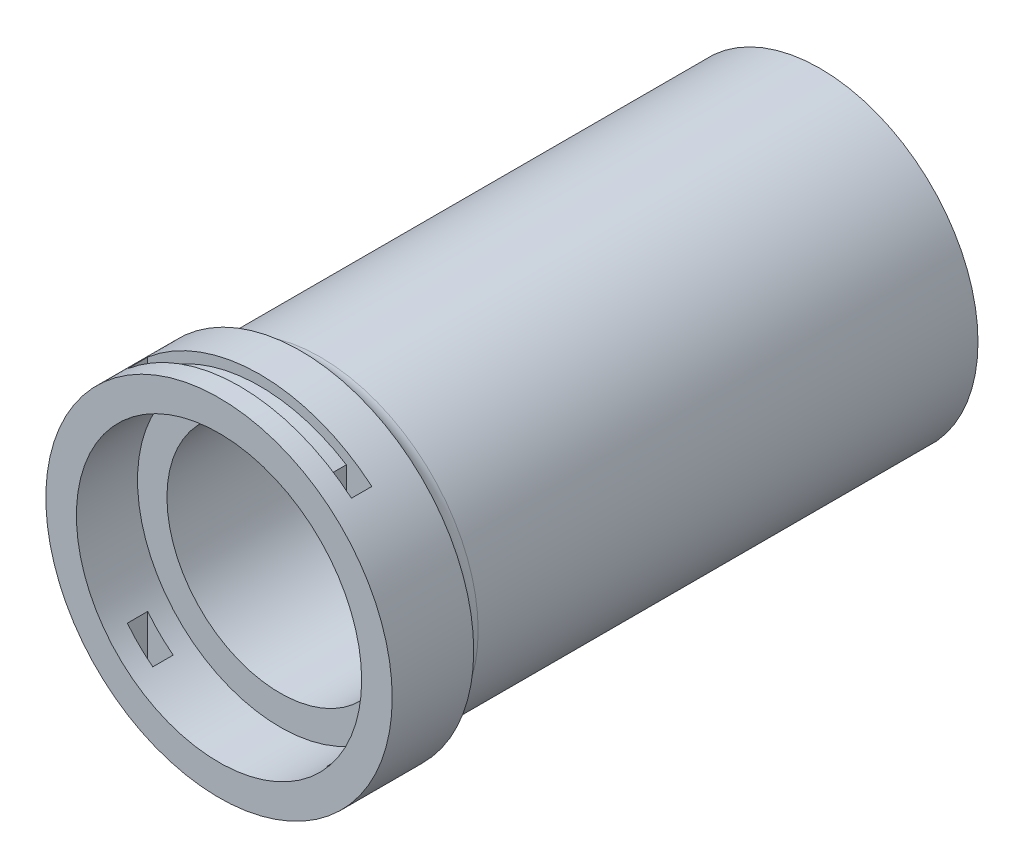
SolidWorks part; units mm, degrees
material "ABS"
ref_plane "Front Plane" through (0, 0, 0) normal (0, 0, 1) x (1, 0, 0)
ref_plane "Top Plane" through (0, 0, 0) normal (0, 1, 0) x (1, 0, 0)
ref_plane "Right Plane" through (0, 0, 0) normal (1, 0, 0) x (0, 0, -1)
sketch "Sketch1" plane through (0, 0, 0) normal (0, 0, 1) x (1, 0, 0)
  circle A0 centre (0, 0) radius 15.5
  dimension "D1" = 31
extrude "Boss-Extrude5" add sketch "Sketch1" along normal blind 26 contours A0
sketch "Sketch3" plane through (0, 0, 26) normal (0, 0, 1) x (1, 0, 0)
  circle A0 centre (0, 0) radius 5.625
  dimension "D1" = 11.25
extrude "Cut-Extrude2" cut sketch "Sketch3" against normal through all
sketch "Sketch4" plane through (0, 0, 26) normal (0, 0, 1) x (1, 0, 0)
  circle A0 centre (0, 0) radius 11.1125
  circle A2 centre (0, 0) radius 15.5 construction
  dimension "D1" = 22.225
  dimension "D2" = 4.3875
extrude "Cut-Extrude3" cut sketch "Sketch4" against normal blind 20 and the other way blind 28
sketch "Sketch7" plane through (0, 0, 0) normal (0, 0, 1) x (1, 0, 0)
  circle A1 centre (0, 0) radius 11
  circle A2 centre (0, 0) radius 9
  dimension "D1" = 18
  dimension "D2" = 22
extrude "Cut-Extrude6" cut sketch "Sketch7" against normal blind 2 from surface starting at face at (11.1125, 0, 6)
sketch "Sketch12" plane through (0, 0, 0) normal (0, 0, 1) x (1, 0, 0)
  circle A0 centre (0, 0) radius 17
  dimension "D1" = 34
extrude "Boss-Extrude8" add sketch "Sketch12" along normal up to surface (26 mm away) and the other way blind 2 from offset 20 up to face at (15.5, 0, 26)
sketch "Sketch13" plane through (0, 0, 0) normal (0, 0, 1) x (1, 0, 0)
  circle A0 centre (0, 0) radius 11
extrude "Cut-Extrude10" cut sketch "Sketch13" along normal through all from surface starting at face at (11.1125, 0, 18)
fillet "Fillet2" radius 2 1 edges at (15.5, 0, 18)
sketch "Sketch14" plane through (0, 0, 0) normal (0, 0, 1) x (1, 0, 0)
  circle A0 centre (0, 0) radius 14
  dimension "D1" = 28
extrude "Cut-Extrude11" cut sketch "Sketch14" against normal blind 6 from surface starting at face at (17, 0, 26)
sketch "Sketch15" plane through (0, 0, 0) normal (0, 0, 1) x (1, 0, 0)
  circle A0 centre (0, 10) radius 0.5
  circle A1 centre (0, 0) radius 11 construction
  circle A3 centre (0, -10) radius 0.5
  circle A4 centre (10, 0) radius 0.5
  circle A5 centre (-10, 0) radius 0.5
  dimension "D1" = 10
extrude "Cut-Extrude14" cut sketch "Sketch15" along normal through all contours A3 | A4 | A0 | A5
sketch "Sketch18" plane through (0, 0, 0) normal (0, 1, 0) x (1, 0, 0)
  line L0 (-17, -26) -> (17, -26) construction
  line L1 (11, -22) -> (-11, -22) construction
  line L2 (11, -22) -> (11, -24)
  line L3 (11, -24) -> (-11, -24) construction
  line L4 (-11, -22) -> (-11, -24)
  line L5 (11, -22) -> (-11, -24) construction
  line L6 (11, -24) -> (-11, -22) construction
  line L7 (-11, -24) -> (-8.5, -24)
  line L8 (-11, -24) -> (-11, -22)
  line L9 (-11, -22) -> (-8.5, -22)
  line L10 (-8.5, -24) -> (-8.5, -22)
  line L11 (11, -24) -> (8.5, -24)
  line L12 (11, -24) -> (11, -22)
  line L13 (11, -22) -> (8.5, -22)
  line L14 (8.5, -24) -> (8.5, -22)
  line L15 (-11, -22) -> (-8.5, -22)
  line L16 (-11, -24) -> (-8.5, -24)
  line L17 (8.5, -22) -> (11, -22)
  line L18 (8.5, -24) -> (11, -24)
  point P0 (0, -23)
  dimension "D1" = 2
  dimension "D2" = 2.5
  dimension "D3" = 2.5
  dimension "D4" = 17
  dimension "D5" = 0
  dimension "D6" = 2
extrude "Cut-Extrude15" cut sketch "Sketch18" against normal mid plane 40 contours L7 L10 L9 L4 | L14 L11 L2 L13 region at (9.75, 0, 23) region at (-9.75, 0, 23)
ref_plane "Plane1" through (0, 0, 24) normal (0, 0, -1) x (-1, 0, 0)
sketch "Sketch23" plane through (0, 0, 24) normal (0, 0, -1) x (-1, 0, 0)
  line L0 (9.7192, 13.9477) -> (9.1475, 13.1272)
  line L1 (-9.1475, 13.1272) -> (-9.7192, 13.9477)
  line L2 (-9.1475, -13.1272) -> (-9.7192, -13.9477)
  line L3 (9.7192, -13.9477) -> (9.1475, -13.1272)
  arc A0 (9.1475, 13.1272) -> (-9.1475, 13.1272) centre (0, 0) ccw
  arc A1 (9.1475, -13.1272) -> (-9.1475, -13.1272) centre (0, 0) cw
  arc A2 (9.7192, 13.9477) -> (-9.7192, 13.9477) centre (0, 0) ccw
  arc A3 (-9.7192, -13.9477) -> (9.7192, -13.9477) centre (0, 0) ccw
  dimension "D1" = 1
  dimension "D2" = 17
extrude "Cut-Extrude16" cut sketch "Sketch23" along normal blind 2
sketch "Sketch24" plane through (0, 0, 6) normal (0, 0, 1) x (1, 0, 0)
  circle A0 centre (0, 0) radius 9
  circle A1 centre (0, 0) radius 5.625
  dimension "D1" = 11.25
  dimension "D2" = 18
sketch "Sketch26" plane through (0, 0, 0) normal (0, 0, -1) x (-1, 0, 0)
  circle A0 centre (0, 0) radius 15.5
  circle A1 centre (0, 0) radius 5.625
  circle A2 centre (-10, 0) radius 0.5
  circle A3 centre (0, 10) radius 0.5
  circle A4 centre (10, 0) radius 0.5
  circle A5 centre (0, -10) radius 0.5
  point P16 (0, 0)
  dimension "D1" = 1
  dimension "D2" = 11.25
  dimension "D3" = 31
  dimension "D5" = 10
  dimension "D6" = 10
  dimension "D4" = 4
extrude "Boss-Extrude9" add sketch "Sketch26" along normal blind 33
sketch "Sketch27" plane through (0, 0, 4) normal (0, 0, 1) x (1, 0, 0)
  circle A0 centre (0, 0) radius 11.1125
  dimension "D1" = 22.225
extrude "Cut-Extrude17" cut sketch "Sketch27" against normal mid plane 66
extrude "Boss-Extrude10" add sketch "Sketch24" against normal blind 35 contours A1 | A0
